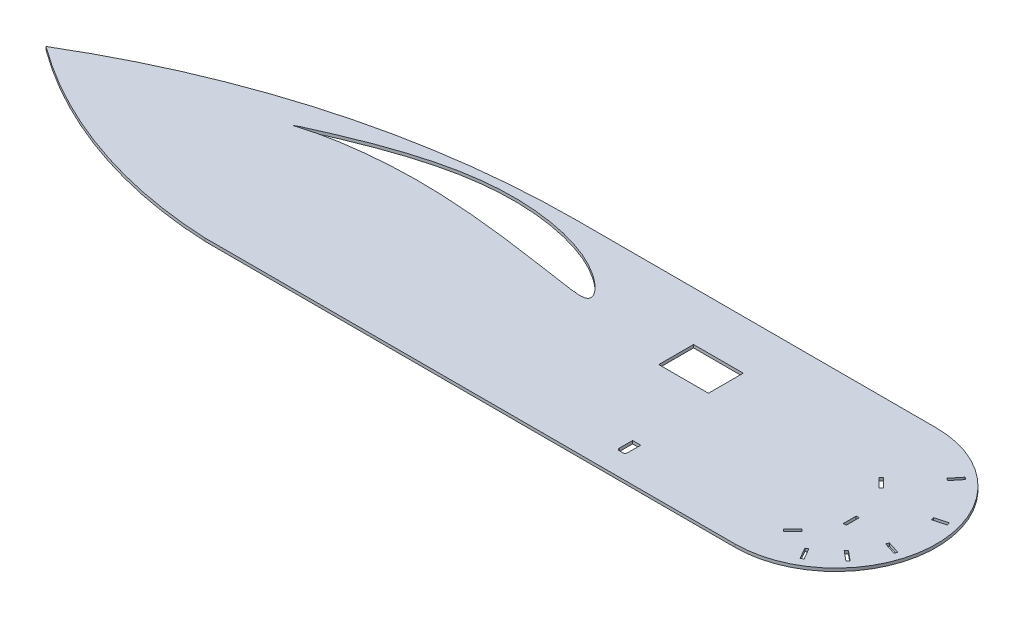
SolidWorks part; units mm, degrees
ref_plane "Front Plane" through (0, 0, 0) normal (0, 0, 1) x (1, 0, 0)
ref_plane "Top Plane" through (0, 0, 0) normal (0, 1, 0) x (1, 0, 0)
ref_plane "Right Plane" through (0, 0, 0) normal (1, 0, 0) x (0, 0, -1)
sketch "Sketch1" plane through (0, 0, 0) normal (0, 1, 0) x (1, 0, 0)
  line L0 (800, 101.2493) -> (0, 101.2493) construction
  line L1 (266.4083, 0) -> (800, 0)
  line L2 (0, 0) -> (0, 202.4986) construction
  line L3 (438.3192, 202.4986) -> (800, 202.4986)
  arc A0 (800, 202.4986) -> (800, 0) centre (800, 101.2493) cw
  arc A2 (266.4083, 0) -> (19.4291, 86.8932) centre (286.1808, 450.645) cw
  arc A4 (19.4291, 86.8932) -> (438.3192, 202.4986) centre (438.3192, -614.2173) cw
  dimension "D1" = 800
extrude "Boss-Extrude1" add sketch "Sketch1" along normal blind 3
sketch "Sketch2" plane through (0, 0, 0) normal (0, -1, 0) x (1, 0, 0)
  line L0 (605.07, -153) -> (605.07, 81) construction
  line L1 (655.07, -153) -> (605.07, -153)
  line L2 (655.07, -153) -> (655.07, -118)
  line L3 (655.07, -118) -> (605.07, -118)
  line L4 (823.6893, -121.2328) -> (814.4969, -130.4252)
  line L5 (814.4969, -130.4252) -> (816.6182, -132.5465)
  line L6 (816.6182, -132.5465) -> (825.8106, -123.3541)
  line L7 (825.8106, -123.3541) -> (823.6893, -121.2328)
  line L8 (823.6893, -121.2328) -> (814.4969, -130.4252)
  line L9 (814.4969, -130.4252) -> (816.6182, -132.5465)
  line L10 (816.6182, -132.5465) -> (825.8106, -123.3541)
  line L11 (825.8106, -123.3541) -> (823.6893, -121.2328)
  line L12 (605.07, -153) -> (605.07, -118)
  line L20 (841.1972, -32.9616) -> (847.702, -21.706)
  line L21 (847.702, -21.706) -> (845.1046, -20.2049)
  line L22 (845.1046, -20.2049) -> (838.5998, -31.4605)
  line L23 (838.5998, -31.4605) -> (841.1972, -32.9616)
  line L24 (841.1972, -32.9616) -> (847.702, -21.706)
  line L25 (847.702, -21.706) -> (845.1046, -20.2049)
  line L26 (845.1046, -20.2049) -> (838.5998, -31.4605)
  line L27 (838.5998, -31.4605) -> (841.1972, -32.9616)
  line L28 (839.4566, -85.3169) -> (839.4566, -72.3169)
  line L29 (839.4566, -72.3169) -> (836.4566, -72.3169)
  line L30 (836.4566, -72.3169) -> (836.4566, -85.3169)
  line L31 (836.4566, -85.3169) -> (839.4566, -85.3169)
  line L32 (839.4566, -85.3169) -> (839.4566, -72.3169)
  line L33 (839.4566, -72.3169) -> (836.4566, -72.3169)
  line L34 (836.4566, -72.3169) -> (836.4566, -85.3169)
  line L35 (836.4566, -85.3169) -> (839.4566, -85.3169)
  line L37 (212.57, -142.2618) -> (212.57, -142.2948)
  line L38 (212.57, -142.2618) -> (212.57, -142.2948)
  line L40 (658.07, -25.4734) -> (658.07, -38.6734)
  line L41 (663.77, -22.9734) -> (660.57, -22.9734)
  line L42 (666.27, -38.6734) -> (666.27, -25.4734)
  line L43 (658.07, -38.6734) -> (666.27, -38.6734)
  line L44 (658.07, -25.4734) -> (658.07, -38.6734)
  line L45 (663.77, -22.9734) -> (660.57, -22.9734)
  line L46 (666.27, -38.6734) -> (666.27, -25.4734)
  line L47 (658.07, -38.6734) -> (666.27, -38.6734)
  line L188 (849.2146, -164.0056) -> (857.4278, -174.0824) construction
  line L189 (857.4278, -174.0824) -> (859.7532, -172.1871) construction
  line L190 (859.7532, -172.1871) -> (851.54, -162.1102) construction
  line L191 (851.54, -162.1102) -> (849.2146, -164.0056) construction
  line L192 (876.7598, -122.8909) -> (889.3361, -126.1826) construction
  line L193 (889.3361, -126.1826) -> (890.0958, -123.2804) construction
  line L194 (890.0958, -123.2804) -> (877.5194, -119.9887) construction
  line L195 (877.5194, -119.9887) -> (876.7598, -122.8909) construction
  line L196 (876.494, -78.6863) -> (888.8916, -74.7746) construction
  line L197 (888.8916, -74.7746) -> (887.9888, -71.9136) construction
  line L198 (887.9888, -71.9136) -> (875.5913, -75.8253) construction
  line L199 (875.5913, -75.8253) -> (876.494, -78.6863) construction
  line L200 (862.3792, -51.5576) -> (872.3932, -43.2678) construction
  line L201 (872.3932, -43.2678) -> (870.4801, -40.9569) construction
  line L202 (870.4801, -40.9569) -> (860.4662, -49.2467) construction
  line L203 (860.4662, -49.2467) -> (862.3792, -51.5576) construction
  line L204 (822.4089, -44.7346) -> (813.2165, -35.5422) construction
  line L205 (813.2165, -35.5422) -> (811.0952, -37.6635) construction
  line L206 (811.0952, -37.6635) -> (820.2876, -46.8559) construction
  line L207 (820.2876, -46.8559) -> (822.4089, -44.7346) construction
  line L208 (849.2146, -164.0056) -> (857.4278, -174.0824)
  line L209 (857.4278, -174.0824) -> (859.7532, -172.1871)
  line L210 (859.7532, -172.1871) -> (851.54, -162.1102)
  line L211 (851.54, -162.1102) -> (849.2146, -164.0056)
  line L212 (876.7598, -122.8909) -> (889.3361, -126.1826)
  line L213 (889.3361, -126.1826) -> (890.0958, -123.2804)
  line L214 (890.0958, -123.2804) -> (877.5194, -119.9887)
  line L215 (877.5194, -119.9887) -> (876.7598, -122.8909)
  line L216 (876.494, -78.6863) -> (888.8916, -74.7746)
  line L217 (888.8916, -74.7746) -> (887.9888, -71.9136)
  line L218 (887.9888, -71.9136) -> (875.5913, -75.8253)
  line L219 (875.5913, -75.8253) -> (876.494, -78.6863)
  line L220 (862.3792, -51.5576) -> (872.3932, -43.2678)
  line L221 (872.3932, -43.2678) -> (870.4801, -40.9569)
  line L222 (870.4801, -40.9569) -> (860.4662, -49.2467)
  line L223 (860.4662, -49.2467) -> (862.3792, -51.5576)
  line L224 (822.4089, -44.7346) -> (813.2165, -35.5422)
  line L225 (813.2165, -35.5422) -> (811.0952, -37.6635)
  line L226 (811.0952, -37.6635) -> (820.2876, -46.8559)
  line L227 (820.2876, -46.8559) -> (822.4089, -44.7346)
  arc A2 (660.57, -22.9734) -> (658.07, -25.4734) centre (660.57, -25.4734) ccw
  arc A3 (666.27, -25.4734) -> (663.77, -22.9734) centre (663.77, -25.4734) ccw
  arc A4 (660.57, -22.9734) -> (658.07, -25.4734) centre (660.57, -25.4734) ccw
  arc A5 (666.27, -25.4734) -> (663.77, -22.9734) centre (663.77, -25.4734) ccw
  spline S1 degree 3 poles (-2043.9918, -3443.4247) (189.5826, -75.7884) (189.6368, -128.823) (215.6642, -144.2206) (218.7234, -145.7779) (222.7838, -147.5804) (227.7591, -149.7808) (233.6732, -152.3729) (243.3346, -156.474) (254.0716, -160.9286) (265.8113, -165.5514) (275.5598, -169.1926) (285.8203, -172.7897) (300.2132, -177.4429) (315.0475, -181.6144) (330.2168, -185.0782) (341.7168, -187.2628) (353.2384, -188.9705) (364.7498, -190.1898) (376.2222, -190.8893) (387.6115, -191.0869) (398.8538, -190.7647) (413.4214, -189.6963) (427.5808, -187.7) (441.1954, -184.8275) (450.8219, -182.3197) (459.9489, -179.4697) (468.5117, -176.2876) (476.4536, -172.8247) (483.7151, -169.1289) (490.2481, -165.2848) (496.0197, -161.4069) (500.998, -157.5857) (505.1476, -153.8841) (508.4473, -150.3827) (510.8522, -147.1808) (512.2305, -144.519) (512.6724, -142.438) (512.366, -140.694) (510.8363, -139.2679) (508.3008, -138.6046) (504.9907, -138.3969) (500.8451, -138.6329) (495.8864, -139.207) (490.1274, -140.0338) (483.6007, -141.0142) (476.346, -142.082) (468.4189, -143.2709) (459.8696, -144.553) (447.4042, -146.414) (434.3028, -148.292) (413.2306, -151.0803) (394.9165, -153.1705) (372.4131, -155.1852) (353.2786, -156.4974) (334.1039, -157.1205) (318.8375, -157.1193) (307.5693, -156.8631) (296.5448, -156.3424) (285.8536, -155.5986) (275.5863, -154.6546) (265.8296, -153.5569) (256.6735, -152.3128) (248.205, -150.9585) (240.5101, -149.5233) (233.6661, -148.0641) (227.7356, -146.6296) (222.7715, -145.2056) (218.7746, -143.9126) (215.7248, -142.9952) (188.0736, -136.0031) (152.9714, -169.0838) (969.2071, 3783.6173) knots -0.133659 -0.133659 -0.133659 -0.133659 0.001413 0.005226 0.010781 0.017816 0.026461 0.036791 0.048686 0.076639 0.092363 0.109003 0.126387 0.144339 0.181313 0.200023 0.218713 0.237261 0.255692 0.274037 0.292193 0.310133 0.327788 0.362002 0.378421 0.394287 0.409543 0.424114 0.437938 0.450942 0.463044 0.474154 0.484165 0.493024 0.500713 0.507126 0.51213 0.514904 0.517171 0.520262 0.524245 0.529498 0.536092 0.544061 0.553363 0.563905 0.575615 0.58842 0.602227 0.616944 0.648676 0.665501 0.718564 0.736789 0.773513 0.810245 0.828489 0.846493 0.864125 0.881249 0.897725 0.913415 0.928184 0.941897 0.954411 0.965603 0.97535 0.983576 0.990285 0.995433 0.9988 1.126552 1.126552 1.126552 1.126552 only from (212.57, -142.2948) to (212.57, -142.2618)
  spline S2 degree 3 poles (212.57, -142.2948) (212.8151, -142.4601) (213.7215, -143.0713) (215.6642, -144.2206) (218.7234, -145.7779) (222.7838, -147.5804) (227.7591, -149.7808) (233.6732, -152.3729) (243.3346, -156.474) (254.0716, -160.9286) (265.8113, -165.5514) (275.5598, -169.1926) (285.8203, -172.7897) (300.2132, -177.4429) (315.0475, -181.6144) (330.2168, -185.0782) (341.7168, -187.2628) (353.2384, -188.9705) (364.7498, -190.1898) (376.2222, -190.8893) (387.6115, -191.0869) (398.8538, -190.7647) (413.4214, -189.6963) (427.5808, -187.7) (441.1954, -184.8275) (450.8219, -182.3197) (459.9489, -179.4697) (468.5117, -176.2876) (476.4536, -172.8247) (483.7151, -169.1289) (490.2481, -165.2848) (496.0197, -161.4069) (500.998, -157.5857) (505.1476, -153.8841) (508.4473, -150.3827) (510.8522, -147.1808) (512.2305, -144.519) (512.6724, -142.438) (512.366, -140.694) (510.8363, -139.2679) (508.3008, -138.6046) (504.9907, -138.3969) (500.8451, -138.6329) (495.8864, -139.207) (490.1274, -140.0338) (483.6007, -141.0142) (476.346, -142.082) (468.4189, -143.2709) (459.8696, -144.553) (447.4042, -146.414) (434.3028, -148.292) (413.2306, -151.0803) (394.9165, -153.1705) (372.4131, -155.1852) (353.2786, -156.4974) (334.1039, -157.1205) (318.8375, -157.1193) (307.5693, -156.8631) (296.5448, -156.3424) (285.8536, -155.5986) (275.5863, -154.6546) (265.8296, -153.5569) (256.6735, -152.3128) (248.205, -150.9585) (240.5101, -149.5233) (233.6661, -148.0641) (227.7356, -146.6296) (222.7715, -145.2056) (218.7746, -143.9126) (215.7248, -142.9952) (213.7534, -142.4967) (212.8162, -142.3107) (212.57, -142.2618) knots 0 0 0 0 0.001413 0.005226 0.010781 0.017816 0.026461 0.036791 0.048686 0.076639 0.092363 0.109003 0.126387 0.144339 0.181313 0.200023 0.218713 0.237261 0.255692 0.274037 0.292193 0.310133 0.327788 0.362002 0.378421 0.394287 0.409543 0.424114 0.437938 0.450942 0.463044 0.474154 0.484165 0.493024 0.500713 0.507126 0.51213 0.514904 0.517171 0.520262 0.524245 0.529498 0.536092 0.544061 0.553363 0.563905 0.575615 0.58842 0.602227 0.616944 0.648676 0.665501 0.718564 0.736789 0.773513 0.810245 0.828489 0.846493 0.864125 0.881249 0.897725 0.913415 0.928184 0.941897 0.954411 0.965603 0.97535 0.983576 0.990285 0.995433 0.9988 1 1 1 1
  point P38 (655.07, -156)
  point P40 (655.07, -153)
  dimension "D6" = 35
  dimension "D1" = 0
  dimension "D2" = 0
  dimension "D3" = 0
  dimension "D4" = 0
  dimension "D5" = 0
extrude "Cut-Extrude1" cut sketch "Sketch2" against normal through all
